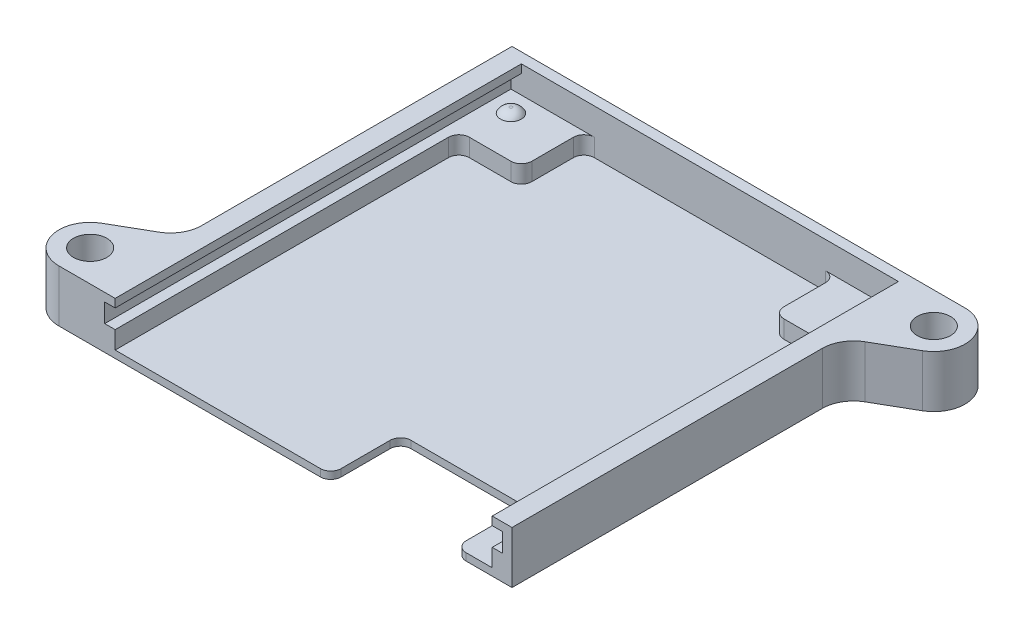
SolidWorks part; units mm, degrees
ref_plane "Front Plane" through (0, 0, 0) normal (0, 0, 1) x (1, 0, 0)
ref_plane "Top Plane" through (0, 0, 0) normal (0, 1, 0) x (1, 0, 0)
ref_plane "Right Plane" through (0, 0, 0) normal (1, 0, 0) x (0, 0, -1)
sketch "Sketch1" plane through (0, 0, 0) normal (0, 1, 0) x (1, 0, 0)
  line L1 (-20, 20) -> (20, 20)
  line L2 (-20, 20) -> (-20, -20)
  line L3 (-20, -20) -> (20, -20)
  line L4 (20, 20) -> (20, -20)
  line L5 (-20, 20) -> (20, -20) construction
  line L6 (-20, -20) -> (20, 20) construction
  point P0 (0, 0)
  dimension "D1" = 40
extrude "Boss-Extrude1" add sketch "Sketch1" along normal blind 5
sketch "Sketch3" plane through (0, 0, 20) normal (0, 0, 1) x (1, 0, 0)
  line L0 (-18.1, 5) -> (-18.1, 4.2)
  line L1 (-20, 5) -> (20, 5) construction
  line L2 (-18.1, 4.2) -> (-19.1, 4.2)
  line L3 (-19.1, 4.2) -> (-19.1, 2.4)
  line L4 (-19.1, 2.4) -> (-18.1, 2.4)
  line L5 (-18.1, 2.4) -> (-18.1, 0.7)
  line L6 (-18.1, 0.7) -> (18.1, 0.7)
  line L7 (-18.1, 5) -> (18.1, 5)
  line L8 (0, 5) -> (0, 0) construction
  line L9 (-20, 0) -> (20, 0) construction
  line L10 (18.1, 2.4) -> (18.1, 0.7)
  line L11 (19.1, 2.4) -> (18.1, 2.4)
  line L12 (19.1, 4.2) -> (19.1, 2.4)
  line L13 (18.1, 4.2) -> (19.1, 4.2)
  line L14 (18.1, 5) -> (18.1, 4.2)
  point P13 (0, 0)
  point P16 (0, 0.7)
  dimension "D1" = 38.2
  dimension "D2" = 1
  dimension "D3" = 0.8
  dimension "D4" = 1.8
  dimension "D5" = 3.5
extrude "Cut-Extrude2" cut sketch "Sketch3" against normal blind 39
sketch "Sketch4" plane through (0, 0.7, 0) normal (0, 1, 0) x (1, 0, 0)
  line L0 (-18.1, -20) -> (18.1, -20) construction
  line L1 (2.6, -20) -> (14.6, -20)
  line L2 (2.6, -20) -> (2.6, -13.3)
  line L3 (2.6, -13.3) -> (14.6, -13.3)
  line L4 (14.6, -20) -> (14.6, -13.3)
  line L5 (19.1, 19) -> (19.1, -20) construction
  dimension "D1" = 12
  dimension "D2" = 16.5
  dimension "D3" = 6.7
extrude "Cut-Extrude3" cut sketch "Sketch4" against normal through all
sketch "Sketch5" plane through (0, 0.7, 0) normal (0, 1, 0) x (1, 0, 0)
  line L1 (-18.1, 19) -> (-12.1, 19)
  line L2 (-18.1, 19) -> (-18.1, 13)
  line L3 (-18.1, 13) -> (-12.1, 13)
  line L4 (-12.1, 19) -> (-12.1, 13)
  line L5 (18.1, 19) -> (12.1, 19)
  line L6 (18.1, 19) -> (18.1, 13)
  line L7 (18.1, 13) -> (12.1, 13)
  line L8 (12.1, 19) -> (12.1, 13)
  dimension "D1" = 6
extrude "Boss-Extrude2" add sketch "Sketch5" along normal up to vertex (1.7 mm away) up to point (18.1, 2.4, -19)
fillet "Fillet1" radius 1 10 edges at (2.6, 0.35, 20) (14.6, 0.35, 20) (14.6, 0.35, 13.3) (2.6, 0.35, 13.3) (12.1, 1.55, -13) (18.1, 1.55, -13) (-12.1, 1.55, -13) (-12.1, 1.55, -19) (12.1, 1.55, -19) (-18.1, 1.55, -13)
sketch "Sketch6" plane through (0, 2.4, 0) normal (0, 1, 0) x (1, 0, 0)
  line L0 (-19.1, 19) -> (-11.1, 19) construction
  line L1 (-19.1, 19) -> (-19.1, -20) construction
  line L2 (11.1, 19) -> (19.1, 19) construction
  line L3 (19.1, 19) -> (19.1, -20) construction
  circle A0 centre (-17.1, 17) radius 1
  circle A1 centre (17.1, 17) radius 1
  dimension "D1" = 2
  dimension "D2" = 2
  dimension "D3" = 2
  dimension "D4" = 2
  dimension "D5" = 2
extrude "Boss-Extrude3" add sketch "Sketch6" along normal blind 0.5
fillet "Fillet2" radius 1 2 edges at (16.1, 2.9, -17) (-18.1, 2.9, -17)
sketch "Sketch7" plane through (0, 0, 0) normal (0, -1, 0) x (1, 0, 0)
  line L0 (-20, 20) -> (-20, 11.5215)
  line L1 (-20, -20) -> (-20, 20) construction
  line L2 (-20, 11.5215) -> (-24.9975, 14.4005)
  line L3 (-23.5, 20) -> (-20, 20)
  line L4 (20, -20) -> (20, -11.5215)
  line L5 (20, 20) -> (20, -20) construction
  line L6 (20, -11.5215) -> (24.9975, -14.4005)
  line L7 (23.5, -20) -> (20, -20)
  arc A0 (-24.9975, 14.4005) -> (-23.5, 20) centre (-23.5, 17) cw
  arc A1 (24.9975, -14.4005) -> (23.5, -20) centre (23.5, -17) cw
  circle A2 centre (-23.5, 17) radius 1.6
  circle A3 centre (23.5, -17) radius 1.6
  dimension "D1" = 3.2
  dimension "D2" = 3
  dimension "D3" = 3.5
extrude "Boss-Extrude4" add sketch "Sketch7" against normal up to vertex (5 mm away) up to point (-20, 5, -20)
fillet "Fillet3" radius 3 2 edges at (20, 2.5, -11.5215) (-20, 2.5, 11.5215)
